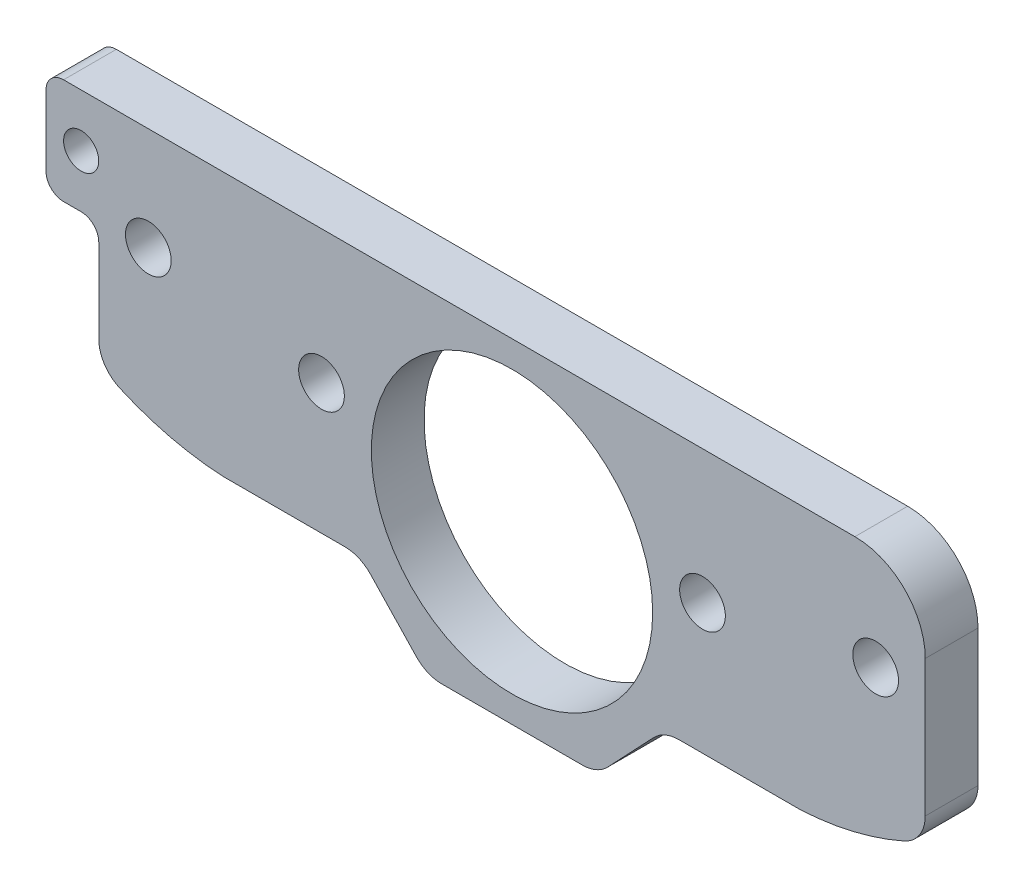
SolidWorks part; units mm, degrees
ref_plane "Front" through (0, 0, 0) normal (0, 0, 1) x (1, 0, 0)
ref_plane "Top" through (0, 0, 0) normal (0, 1, 0) x (1, 0, 0)
ref_plane "Right" through (0, 0, 0) normal (1, 0, 0) x (0, 0, -1)
sketch "Эскиз1" plane through (0, 0, 0) normal (0, 0, 1) x (1, 0, 0)
  line L0 (-2.5263, 8.6597) -> (-2.5263, -10.3403) construction
  line L1 (-6.5184, -10.3403) -> (1.4657, -10.3403)
  line L3 (-22.0263, 8.6597) -> (16.9737, 8.6597)
  line L5 (-26.0263, -3.0984) -> (-26.0263, 1.6597)
  line L6 (20.9737, 4.6597) -> (20.9737, -3.0984)
  line L7 (-2.5263, -0.8403) -> (-23.2073, 2.8063) construction
  line L8 (-22.0263, 8.6597) -> (-28.0263, 8.6597)
  line L9 (-29.0263, 7.6597) -> (-29.0263, 3.6597)
  line L10 (-28.0263, 2.6597) -> (-27.0263, 2.6597)
  line L11 (-18.9453, -6.3403) -> (-12.0263, -6.3403)
  line L12 (-10.5739, -6.9654) -> (-7.9708, -9.7153)
  line L13 (5.5212, -6.9654) -> (2.9181, -9.7153)
  line L14 (13.8926, -6.3403) -> (6.9737, -6.3403)
  circle A0 centre (-2.5263, -0.8403) radius 8
  arc A4 (16.9737, 8.6597) -> (20.9737, 4.6597) centre (16.9737, 4.6597) cw
  circle A5 centre (-23.2073, 2.8063) radius 1.3
  circle A6 centre (-13.3592, 1.0698) radius 1.3
  circle A7 centre (8.3066, 1.0698) radius 1.3
  circle A8 centre (18.1546, 2.8063) radius 1.3
  arc A9 (-26.0263, 1.6597) -> (-27.0263, 2.6597) centre (-27.0263, 1.6597) ccw
  arc A10 (-28.0263, 8.6597) -> (-29.0263, 7.6597) centre (-28.0263, 7.6597) ccw
  arc A11 (-29.0263, 3.6597) -> (-28.0263, 2.6597) centre (-28.0263, 3.6597) ccw
  circle A12 centre (-27.0263, 5.6597) radius 1
  arc A14 (5.5212, -6.9654) -> (6.9737, -6.3403) centre (6.9737, -8.3403) cw
  arc A15 (2.9181, -9.7153) -> (1.4657, -10.3403) centre (1.4657, -8.3403) cw
  arc A16 (-7.9708, -9.7153) -> (-6.5184, -10.3403) centre (-6.5184, -8.3403) ccw
  arc A17 (-12.0263, -6.3403) -> (-10.5739, -6.9654) centre (-12.0263, -8.3403) cw
  arc A19 (-24.8389, -4.9259) -> (-18.9453, -6.3403) centre (-18.0678, 10.3016) ccw
  arc A20 (19.7863, -4.9259) -> (13.8926, -6.3403) centre (13.0152, 10.3016) cw
  arc A21 (20.9737, -3.0984) -> (19.7863, -4.9259) centre (18.9737, -3.0984) cw
  arc A22 (-26.0263, -3.0984) -> (-24.8389, -4.9259) centre (-24.0263, -3.0984) ccw
  point P9 (20.9737, -6.3403)
  point P11 (20.9737, -10.3403)
  point P13 (20.9737, -4.3403)
  point P14 (-26.0263, -10.3403)
  point P17 (-26.0263, 8.6597)
  point P20 (20.9737, 8.6597)
  point P41 (-27.5263, 2.6597)
  point P43 (6.1129, -6.3403)
  point P46 (2.3264, -10.3403)
  point P49 (-7.3791, -10.3403)
  point P52 (-11.1656, -6.3403)
  point P55 (-26.0263, -6.3403)
  point P61 (-26.0263, -4.3403)
  dimension "D1" = 16
  dimension "D4" = 14
  dimension "D5" = 10
  dimension "D10" = 1
  dimension "D11" = 3
  dimension "D2" = 2
  dimension "D3" = 47
  dimension "D6" = 9.5
  dimension "D7" = 80
  dimension "D8" = 11
  dimension "D9" = 19
  dimension "D12" = 2
  dimension "D14" = 3
  dimension "D15" = 6
extrude "Бобышка-Вытянуть1" add sketch "Эскиз1" along normal blind 3
